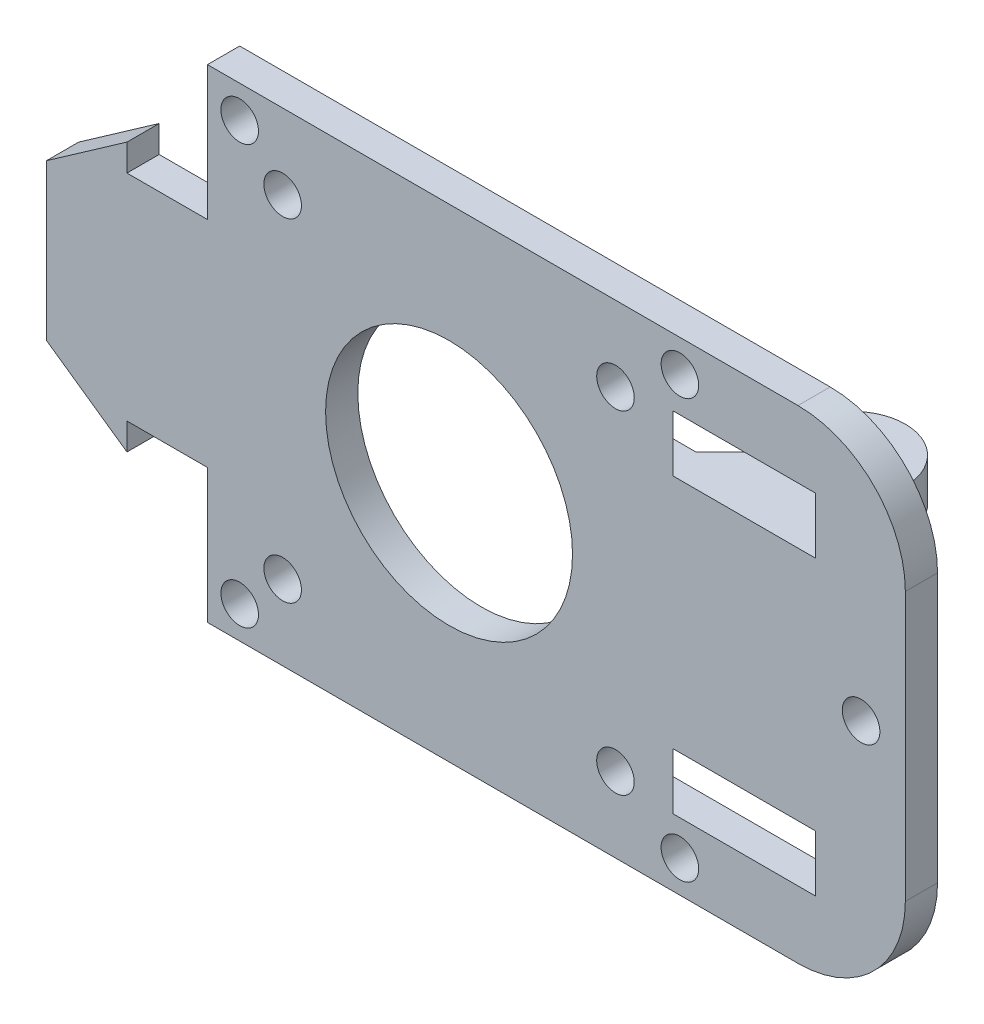
SolidWorks part; units mm, degrees
ref_plane "Front Plane" through (0, 0, 0) normal (0, 0, 1) x (1, 0, 0)
ref_plane "Top Plane" through (0, 0, 0) normal (0, 1, 0) x (1, 0, 0)
ref_plane "Right Plane" through (0, 0, 0) normal (1, 0, 0) x (0, 0, -1)
sketch "Sketch1" plane through (0, 0, 0) normal (0, 0, 1) x (1, 0, 0)
  line L1 (-44.437, 19.3432) -> (20.563, 19.3432)
  line L2 (-44.437, 19.3432) -> (-44.437, -25.6568)
  line L3 (-44.437, -25.6568) -> (20.563, -25.6568)
  line L4 (20.563, 19.3432) -> (20.563, -25.6568)
  dimension "D1" = 65
  dimension "D2" = 45
extrude "Boss-Extrude1" add sketch "Sketch1" along normal blind 3
fillet "Fillet4" radius 10 2 edges at (20.563, -25.6568, 1.5) (20.563, 19.3432, 1.5)
sketch "Sketch8" plane through (0, 0, 0) normal (0, 0, -1) x (-1, 0, 0)
  line L0 (44.437, 19.3432) -> (44.437, -25.6568) construction
  line L1 (44.437, 9.3432) -> (59.437, 9.3432) construction
  line L2 (44.437, 9.3432) -> (44.437, -15.6568) construction
  line L3 (44.437, -15.6568) -> (59.437, -15.6568) construction
  line L4 (59.437, 9.3432) -> (59.437, -15.6568) construction
  line L5 (-10.563, 19.3432) -> (44.437, 19.3432) construction
  line L6 (44.437, -25.6568) -> (-10.563, -25.6568) construction
  line L7 (51.937, 9.3432) -> (51.937, -15.6568) construction
  line L8 (44.437, 6.8432) -> (51.937, 6.8432)
  line L9 (44.437, -13.1568) -> (51.937, -13.1568)
  line L10 (51.937, -15.6568) -> (59.437, -10.4053)
  line L11 (51.937, 9.3432) -> (59.437, 4.0916)
  line L12 (44.437, 6.8432) -> (44.437, -13.1568)
  line L13 (51.937, 9.3432) -> (51.937, 6.8432)
  line L14 (51.937, -13.1568) -> (51.937, -15.6568)
  line L15 (59.437, 4.0916) -> (59.437, -10.4053)
  dimension "D1" = 10
  dimension "D2" = 10
  dimension "D3" = 15
  dimension "D4" = 2.5
  dimension "D5" = 2.5
  dimension "D6" = 55
  dimension "D7" = 55
extrude "Boss-Extrude4" add sketch "Sketch8" against normal blind 3 contours L11 L15 L10 L14 L9 L12 L8 L13
sketch "Sketch2" plane through (0, 0, 0) normal (0, 0, -1) x (-1, 0, 0)
  line L0 (-10.563, 3.8432) -> (-10.563, 7.8432)
  line L5 (-0.563, -10.1568) -> (-10.563, -10.1568) construction
  line L6 (-0.563, -10.1568) -> (-0.563, 3.8432) construction
  line L7 (-0.563, 3.8432) -> (-10.563, 3.8432) construction
  line L8 (-10.563, -10.1568) -> (-10.563, 3.8432) construction
  line L9 (-10.563, 7.8432) -> (-0.563, 7.8432)
  line L10 (-20.563, -3.1568) -> (70.0438, -3.1568) construction
  line L11 (-20.563, -15.6568) -> (-20.563, 9.3432) construction
  line L12 (-0.563, 7.8432) -> (-0.563, 3.8432)
  line L13 (-0.563, 3.8432) -> (-10.563, 3.8432)
  line L14 (-0.563, -14.1568) -> (-0.563, -10.1568)
  line L15 (-10.563, -14.1568) -> (-0.563, -14.1568)
  line L16 (-10.563, -10.1568) -> (-10.563, -14.1568)
  line L17 (-0.563, -10.1568) -> (-10.563, -10.1568)
  dimension "D1" = 14
  dimension "D2" = 10
  dimension "D4" = 10
  dimension "D5" = 4
sketch "Sketch9" plane through (0, 0, 0) normal (0, 0, -1) x (-1, 0, 0)
  line L0 (0.437, -3.1568) -> (0.437, 24.531) construction
  line L1 (-20.563, -3.1568) -> (70.0438, -3.1568) construction
  line L2 (-20.563, -15.6568) -> (-20.563, 9.3432) construction
  line L3 (0.437, -3.1568) -> (0.437, -31.0588) construction
  line L4 (-33.9259, -22.6568) -> (64.4679, -22.6568) construction
  line L11 (44.437, -25.6568) -> (-10.563, -25.6568) construction
  line L12 (41.437, 30.7387) -> (41.437, -37.8284) construction
  line L13 (44.437, 19.3432) -> (44.437, 6.8432) construction
  line L14 (-26.3067, -3.1568) -> (68.9404, -3.1568) construction
  circle A0 centre (-16.44, -3.1568) radius 1.75
  circle A1 centre (0.437, -22.6568) radius 1.75
  circle A2 centre (41.437, -22.6568) radius 1.75
  circle A3 centre (41.437, 16.3432) radius 1.75
  circle A4 centre (0.437, 16.3432) radius 1.75
  dimension "D7" = 0
  dimension "D1" = 21
  dimension "D6" = 3
  dimension "D8" = 3
extrude "Cut-Extrude5" cut sketch "Sketch9" against normal blind 5
sketch "Sketch10" plane through (0, 0, 0) normal (0, 0, -1) x (-1, 0, 0)
  line L0 (-10.563, 19.3432) -> (44.437, 19.3432) construction
  line L1 (6.437, 12.3432) -> (37.437, 12.3432) construction
  line L2 (6.437, 12.3432) -> (6.437, -18.6568) construction
  line L3 (6.437, -18.6568) -> (37.437, -18.6568) construction
  line L4 (37.437, 12.3432) -> (37.437, -18.6568) construction
  line L5 (44.437, -13.1568) -> (44.437, -25.6568) construction
  line L6 (6.437, 12.3432) -> (37.437, -18.6568) construction
  line L7 (6.437, -18.6568) -> (37.437, 12.3432) construction
  circle A1 centre (6.437, -18.6568) radius 1.75
  circle A2 centre (37.437, 12.3432) radius 1.75
  circle A3 centre (6.437, 12.3432) radius 1.75
  circle A4 centre (37.437, -18.6568) radius 1.75
  circle A6 centre (21.937, -3.1568) radius 11.5
  dimension "D5" = 23
  dimension "D1" = 31
  dimension "D2" = 31
  dimension "D3" = 7
  dimension "D4" = 7
extrude "Cut-Extrude6" cut sketch "Sketch10" against normal blind 5
extrude "Boss-Extrude5" add sketch "Sketch2" along normal blind 12
sketch "Sketch11" plane through (0, -14.1568, 0) normal (0, -1, 0) x (1, 0, 0)
  line L0 (0.563, -2) -> (10.563, -2) construction
  line L1 (0.563, -12) -> (0.563, 0) construction
  line L2 (10.563, -12) -> (10.563, 0) construction
  line L3 (10.563, 0) -> (0.563, 0) construction
  line L4 (0.563, -2) -> (10.563, -12) construction
  line L5 (10.563, -2) -> (0.563, -12) construction
  circle A1 centre (5.563, -7) radius 1.75
  dimension "D1" = 2
extrude "Cut-Extrude7" cut sketch "Sketch11" against normal blind 22
chamfer "Chamfer3" distance 2.5 angle 45 4 edges at (0.563, -12.1568, 0) (0.563, 5.8432, 0) (10.563, -12.1568, 0) (10.563, 5.8432, 0)
chamfer "Chamfer4" distance 5 angle 45 2 edges at (5.563, -10.1568, 0) (5.563, 3.8432, 0)
fillet "Fillet5" radius 5 4 edges at (0.563, -12.1568, -12) (10.563, -12.1568, -12) (0.563, 5.8432, -12) (10.563, 5.8432, -12)
ref_axis "Axis1" through (5.563, 7.8432, -7) along (0, -1, 0)
ref_plane "Plane1" through (5.563, 0, 0) normal (1, 0, 0) x (0, 0, -1)
sketch "Sketch13" plane through (5.563, 0, 0) normal (1, 0, 0) x (0, 0, -1)
  line L0 (7, 7.8432) -> (7, 3.8432) construction
  line L1 (19, 13.0932) -> (7, 13.0932)
  line L2 (19, 13.0932) -> (19, 7.8432)
  line L3 (19, 7.8432) -> (7, 7.8432)
  line L4 (7, 13.0932) -> (7, 7.8432)
  line L5 (12, 7.8432) -> (7, 7.8432) construction
  dimension "D1" = 5.25
  dimension "D2" = 12
  dimension "D3" = 0
  dimension "D4" = 0
revolve "Cut-Revolve1" cut sketch "Sketch13" angle 360 about axis through (5.563, 7.8432, -7) along (0, -1, 0)
ref_plane "Plane2" through (0, -3.1568, 0) normal (0, 1, 0) x (1, 0, 0)
mirror "Mirror1" about plane through (0, -3.1568, 0) normal (0, 1, 0) of "Cut-Revolve1"
